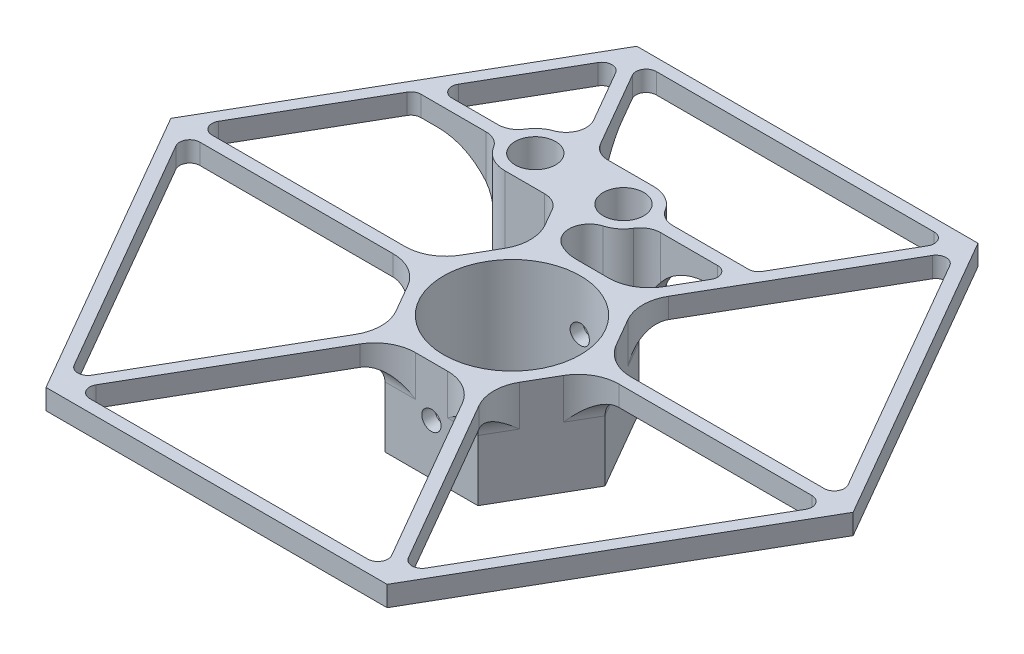
SolidWorks part; units mm, degrees
ref_plane "Alzado" through (0, 0, 0) normal (0, 0, 1) x (1, 0, 0)
ref_plane "Planta" through (0, 0, 0) normal (0, 1, 0) x (1, 0, 0)
ref_plane "Vista lateral" through (0, 0, 0) normal (1, 0, 0) x (0, 0, -1)
sketch "Croquis1" plane through (0, 0, 0) normal (0, 1, 0) x (1, 0, 0)
  line L0 (-33.6595, 58.3) -> (-67.319, 0)
  line L1 (18.3597, 0) -> (9.1799, 15.9)
  line L2 (9.1799, 15.9) -> (-9.1799, 15.9)
  line L3 (-9.1799, 15.9) -> (-18.3597, 0)
  line L4 (-18.3597, 0) -> (-9.1799, -15.9)
  line L5 (-9.1799, -15.9) -> (9.1799, -15.9)
  line L6 (9.1799, -15.9) -> (18.3597, 0)
  line L7 (64.5478, 0) -> (32.2739, 55.9)
  line L8 (32.2739, 55.9) -> (-32.2739, 55.9)
  line L9 (-32.2739, 55.9) -> (-64.5478, 0)
  line L10 (-64.5478, 0) -> (-32.2739, -55.9)
  line L11 (-32.2739, -55.9) -> (32.2739, -55.9)
  line L12 (32.2739, -55.9) -> (64.5478, 0)
  line L13 (-67.319, 0) -> (-33.6595, -58.3)
  line L14 (-33.6595, -58.3) -> (33.6595, -58.3)
  line L15 (33.6595, -58.3) -> (67.319, 0)
  line L16 (67.319, 0) -> (33.6595, 58.3)
  line L17 (33.6595, 58.3) -> (-33.6595, 58.3)
  line L18 (-32.2739, 55.9) -> (-9.1799, 15.9) construction
  line L19 (-64.5478, 0) -> (-18.3597, 0) construction
  line L20 (-32.2739, -55.9) -> (-9.1799, -15.9) construction
  line L21 (9.1799, -15.9) -> (32.2739, -55.9) construction
  line L22 (18.3597, 0) -> (64.5478, 0) construction
  line L23 (9.1799, 15.9) -> (32.2739, 55.9) construction
  line L24 (-32.9667, 54.7) -> (-10.2191, 15.3)
  line L25 (9.8727, 14.7) -> (32.9667, 54.7)
  line L26 (17.6669, -1.2) -> (63.8549, -1.2)
  line L27 (7.7942, -15.9) -> (30.8882, -55.9)
  line L28 (-30.8882, -55.9) -> (-8.1406, -16.5)
  line L29 (-63.8549, -1.2) -> (-18.3597, -1.2)
  line L30 (-30.8882, 55.9) -> (-8.1406, 16.5)
  line L31 (7.7942, 15.9) -> (30.8882, 55.9)
  line L32 (17.6669, 1.2) -> (63.8549, 1.2)
  line L33 (9.8727, -14.7) -> (32.9667, -54.7)
  line L34 (-32.9667, -54.7) -> (-10.2191, -15.3)
  line L35 (-63.8549, 1.2) -> (-18.3597, 1.2)
  line L36 (-31.2346, 56.5) -> (-8.1406, 16.5) construction
  line L37 (-33.3131, 55.3) -> (-10.2191, 15.3) construction
  line L38 (8.1406, 16.5) -> (31.2346, 56.5) construction
  line L39 (10.2191, 15.3) -> (33.3131, 55.3) construction
  line L40 (18.3597, 1.2) -> (64.5478, 1.2) construction
  line L41 (18.3597, -1.2) -> (64.5478, -1.2) construction
  line L42 (10.2191, -15.3) -> (33.3131, -55.3) construction
  line L43 (8.1406, -16.5) -> (31.2346, -56.5) construction
  line L44 (-31.2346, -56.5) -> (-8.1406, -16.5) construction
  line L45 (-33.3131, -55.3) -> (-10.2191, -15.3) construction
  line L46 (-64.5478, -1.2) -> (-18.3597, -1.2) construction
  line L47 (-64.5478, 1.2) -> (-18.3597, 1.2) construction
  line L48 (-8.1406, 16.5) -> (-7.7942, 15.9)
  line L49 (-10.2191, 15.3) -> (-9.8727, 14.7)
  line L50 (-18.3597, 1.2) -> (-17.6669, 1.2)
  line L51 (-18.3597, -1.2) -> (-17.6669, -1.2)
  line L52 (-10.2191, -15.3) -> (-9.8727, -14.7)
  line L53 (-8.1406, -16.5) -> (-7.7942, -15.9)
  line L54 (0, 0) -> (0, 30) construction
  line L55 (0, 30) -> (-8, 30) construction
  line L56 (-25.4, 30) -> (-8, 30) construction
  line L57 (-25.4, 30) -> (-8, 30) construction
  line L60 (-25.4, 36) -> (-8, 36)
  line L61 (-25.4, 24) -> (-8, 24)
  line L62 (-31.4, 30) -> (-47.2273, 30) construction
  line L63 (-2, 30) -> (15.9349, 30) construction
  line L64 (-2.1212, 28.8) -> (15.242, 28.8)
  line L65 (-31.2788, 31.2) -> (-46.5344, 31.2)
  line L66 (-2.1212, 31.2) -> (16.6277, 31.2)
  line L67 (-31.2788, 28.8) -> (-47.9201, 28.8)
  line L68 (-31.4, 31.2) -> (-47.2273, 31.2) construction
  line L69 (-31.4, 28.8) -> (-47.2273, 28.8) construction
  line L70 (-2, 31.2) -> (15.9349, 31.2) construction
  line L71 (-2, 28.8) -> (15.9349, 28.8) construction
  circle A0 centre (0, 0) radius 12.7 construction
  circle A1 centre (0, 0) radius 13.5
  circle A2 centre (0, 0) radius 15.9 construction
  circle A3 centre (0, 0) radius 55.9 construction
  circle A4 centre (-8, 30) radius 1.8
  circle A5 centre (-25.4, 30) radius 1.8
  circle A8 centre (-25.4, 30) radius 4
  circle A9 centre (-8, 30) radius 4
  arc A10 (-25.4, 36) -> (-25.4, 24) centre (-25.4, 30) ccw
  arc A11 (-8, 24) -> (-8, 36) centre (-8, 30) ccw
  point P71 (-16.7, 30)
  dimension "D1" = 25.4
  dimension "D2" = 0.8
  dimension "D3" = 2.4
  dimension "D5" = 40
  dimension "D11" = 3.6
  dimension "D12" = 8
  dimension "D8" = 30
  dimension "D9" = 8
  dimension "D10" = 17.4
  dimension "D13" = 12
  dimension "D4" = 2.4
  dimension "D6" = 1.2
  dimension "D7" = 1.2
  dimension "D14" = 1.2
  dimension "D15" = 1.2
extrude "Saliente-Extruir1" add sketch "Croquis1" against normal blind 20 contours L5 L6 L1 L2 L3 L4 A1 region at (17.5927, 0, 0.3571)
extrude "Saliente-Extruir2" add sketch "Croquis1<3>" against normal blind 16 separate body contours L24 L61 L30 L60 | L61 A11 L60 L30 A9 | A9 A4 | L60 A10 L61 L24 A8 | A8 A5 region at (-4.3389, 0, -25.5161) region at (-17.3205, 0, -30) region at (-20.321, 0, -24.2013) region at (-29.2869, 0, -30) region at (-11.8869, 0, -30)
sketch "Croquis1<3>" plane through (0, 0, 0) normal (0, 1, 0) x (1, 0, 0) same geometry as "Croquis1"
extrude "Saliente-Extruir5" add sketch "Croquis1<5>" against normal blind 4 contours L31 L2 L1 L25 L7 L8 | L16 L17 L0 L13 L14 L15 L12 L11 L10 L9 L8 L7 | L29 L51 L4 L3 L50 L35 L9 L10 | L28 L53 L5 L4 L52 L34 L10 L11 | L33 L6 L5 L27 L11 L12 | L32 L1 L6 L26 L12 L7 | L24 L60 L30 L8 L9 | L61 L24 L49 L3 L2 L48 L30 | A11 L64 L31 L66 | A10 L65 L9 L67 region at (0, 0, -56.5189) region at (41.1073, 0, 0) region at (20.5537, 0, -35.6) region at (20.5537, 0, 35.6) region at (-11.4594, 0, -19.7911) region at (6.9517, 0, -30.0154) region at (-20.5537, 0, 35.6) region at (-26.4307, 0, -45.8038) region at (-41.1073, 0, 0) region at (-39.2985, 0, -29.9825)
sketch "Croquis1<5>" plane through (0, 0, 0) normal (0, 1, 0) x (1, 0, 0) same geometry as "Croquis1"
fillet "Redondeo4" radius 12 3 edges at (-31.4, -4, -30) (-20.7846, -4, -36) (-2, -4, -30)
extrude "Saliente-Extruir7" add sketch "Croquis1<7>" against normal blind 16 contours L61 L24 L49 L3 L2 L48 L30 region at (-11.4594, 0, -19.7911)
sketch "Croquis1<7>" plane through (0, 0, 0) normal (0, 1, 0) x (1, 0, 0) same geometry as "Croquis1"
extrude "Cortar-Extruir1" cut sketch "Croquis1<8>" against normal blind 6 contours A9 A4 | A8 A5 region at (-29.2869, 0, -30) region at (-11.8869, 0, -30)
sketch "Croquis1<8>" plane through (0, 0, 0) normal (0, 1, 0) x (1, 0, 0) same geometry as "Croquis1"
fillet "Redondeo5" radius 4 12 edges at (-18.0133, -4, 0.6) (-18.0133, -4, -0.6) (-9.5263, -4, 15.3) (-8.487, -4, 15.9) (8.487, -4, 15.9) (9.5263, -4, 15.3) (18.0133, -4, 0.6) (18.0133, -4, -0.6) (9.5263, -4, -15.3) (8.487, -4, -15.9) (-9.5263, -16, -15.3) (-8.487, -16, -15.9)
fillet "Redondeo6" radius 8 12 edges at (7.7942, -4, -15.9) (-7.7942, -10, -15.9) (-9.8727, -10, -14.7) (-17.6669, -4, -1.2) (-17.6669, -4, 1.2) (-9.8727, -4, 14.7) (-7.7942, -4, 15.9) (7.7942, -4, 15.9) (9.8727, -4, 14.7) (17.6669, -4, 1.2) (17.6669, -4, -1.2) (9.8727, -4, -14.7)
fillet "Redondeo7" radius 4 8 edges at (-12.4708, -8, -24) (-2.1212, -8, -28.8) (-19.399, -8, -36) (-2.1212, -8, -31.2) (-22.1703, -8, -36) (-31.2788, -8, -31.2) (-31.2788, -8, -28.8) (-15.242, -8, -24)
fillet "Redondeo8" radius 2 16 edges at (32.9667, -2, -54.7) (30.8882, -2, -55.9) (63.8549, -2, -1.2) (63.8549, -2, 1.2) (32.9667, -2, 54.7) (30.8882, -2, 55.9) (-30.8882, -2, 55.9) (-32.9667, -2, 54.7) (-63.8549, -2, 1.2) (15.242, -2, -28.8) (16.6277, -2, -31.2) (-63.8549, -2, -1.2) (-47.9201, -2, -28.8) (-46.5344, -2, -31.2) (-32.9667, -2, -54.7) (-30.8882, -2, -55.9)
sketch "Croquis2" plane through (0, 0, 0) normal (0, 0, 1) x (1, 0, 0)
  line L0 (0, 0) -> (0, -10) construction
  circle A0 centre (0, -10) radius 1.9
  dimension "D2" = 3.8
  dimension "D1" = 10
extrude "Cortar-Extruir2" cut sketch "Croquis2" against normal up to surface (15.9 mm away) from surface up to face at (3.06, -9.3333, -15.9) starting at face at (0, -9, 15.9)
